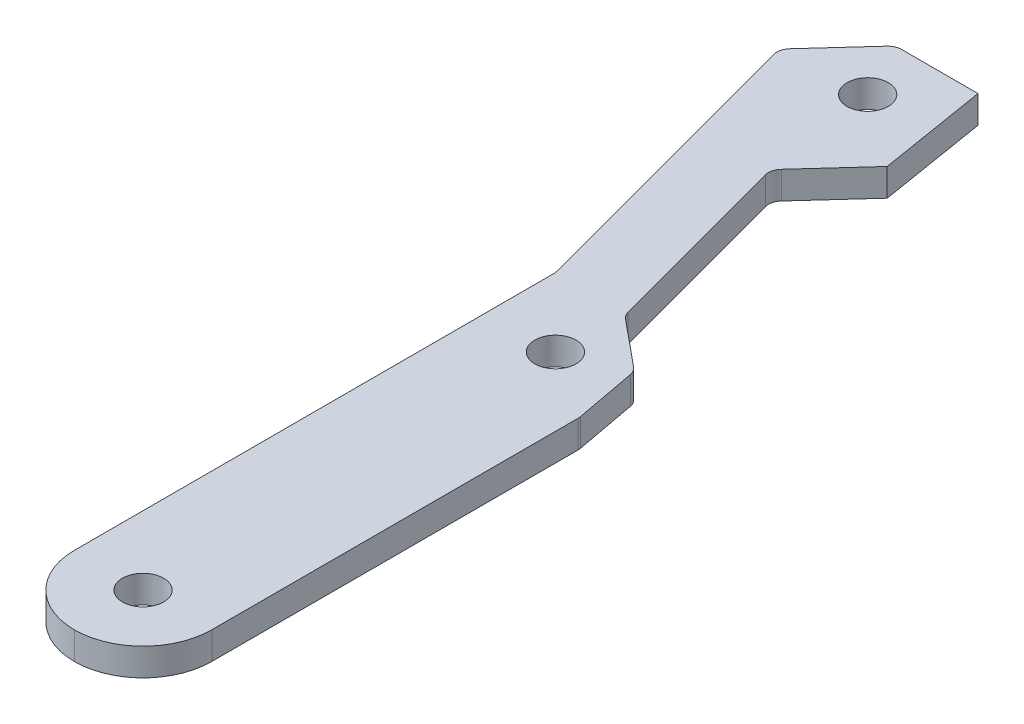
SolidWorks part; units mm, degrees
ref_plane "Front Plane" through (0, 0, 0) normal (0, 0, 1) x (1, 0, 0)
ref_plane "Top Plane" through (0, 0, 0) normal (0, 1, 0) x (1, 0, 0)
ref_plane "Right Plane" through (0, 0, 0) normal (1, 0, 0) x (0, 0, -1)
sketch "Sketch1" plane through (0, 0, 0) normal (0, 1, 0) x (1, 0, 0)
  line L0 (0, 0) -> (10, 0)
  line L1 (0, 0) -> (0, 40)
  line L4 (0, 40) -> (-5.9528, 62.2163)
  line L12 (10, 31.7413) -> (10, 0)
  line L13 (10, 31.7413) -> (9.0831, 36.6565)
  line L14 (9.0831, 36.6565) -> (5.2213, 39.8324)
  line L15 (5.2213, 39.8324) -> (1.339, 54.3213)
  line L16 (-5.9528, 62.2163) -> (-1.9117, 66.6513)
  line L17 (-1.9117, 66.6513) -> (4.0883, 66.6513)
  line L19 (5.3801, 58.7563) -> (1.339, 54.3213)
  line L20 (4.0883, 66.6513) -> (5.3801, 58.7563)
  dimension "D1" = 165
  dimension "D2" = 10
  dimension "D3" = 23
  dimension "D4" = 40
  dimension "D5" = 5
  dimension "D6" = 5
  dimension "D7" = 5
  dimension "D8" = 6
  dimension "15" = 15
  dimension "D9" = 8
  dimension "D10" = 140
  dimension "D11" = 6
  dimension "D12" = 6
extrude "Boss-Extrude1" add sketch "Sketch1" along normal blind 2
fillet "Fillet1" radius 5 2 edges at (10, 1, 0) (0, 1, 0)
sketch "Sketch2" plane through (0, 2, 0) normal (0, 1, 0) x (1, 0, 0)
  line L0 (5, 5) -> (5, 35) construction
  line L1 (5, 35) -> (0.1379, 62.5746) construction
  circle A0 centre (0.1379, 62.5746) radius 1.5
  circle A1 centre (5, 5) radius 1.5
  circle A2 centre (5, 35) radius 1.5
  dimension "D1" = 3
  dimension "D2" = 30
  dimension "D3" = 28
  dimension "D4" = 170
extrude "Cut-Extrude1" cut sketch "Sketch2" against normal through all
fillet "Fillet2" radius 1 7 edges at (-5.9528, 1, -62.2163) (0, 1, -40) (-1.9117, 1, -66.6513) (1.339, 1, -54.3213) (5.2213, 1, -39.8324) (9.0831, 1, -36.6565) (10, 1, -31.7413)
